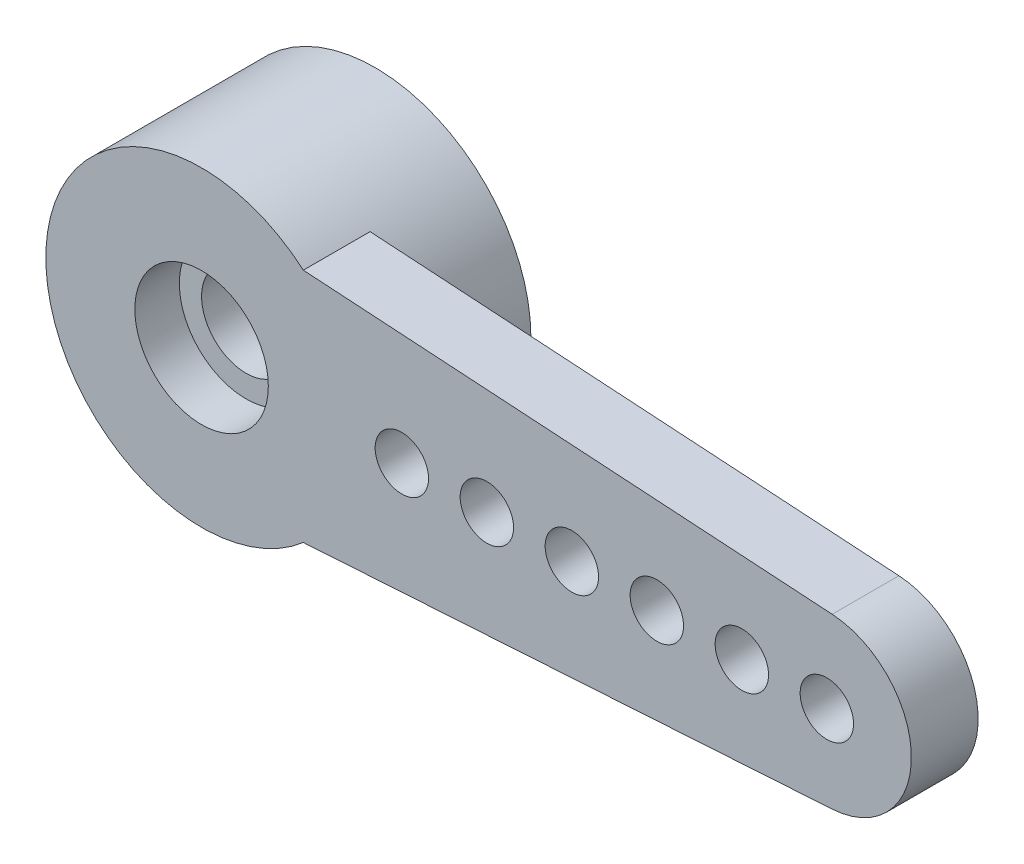
SolidWorks part; units mm, degrees
ref_plane "前视基准面" through (0, 0, 0) normal (0, 0, 1) x (1, 0, 0)
ref_plane "上视基准面" through (0, 0, 0) normal (0, 1, 0) x (1, 0, 0)
ref_plane "右视基准面" through (0, 0, 0) normal (1, 0, 0) x (0, 0, -1)
other "Configuration Table"
sketch "草图1" plane through (0, 0, 0) normal (0, 0, 1) x (1, 0, 0)
  line L12 (15.95, 15.99) -> (15.95, -15.1175) construction
  line L13 (0, 0) -> (14.05, 0) construction
  line L14 (2.2864, 2.65) -> (14.1703, 1.8962)
  line L15 (14.1703, -1.8962) -> (2.2864, -2.65)
  line L16 (2.2864, 2.65) -> (2.2864, -2.65)
  line L17 (4.5, 0) -> (6.41, 0)
  line L18 (6.41, 0) -> (8.32, 0)
  line L19 (8.32, 0) -> (10.23, 0)
  line L20 (10.23, 0) -> (12.14, 0)
  line L21 (12.14, 0) -> (14.05, 0)
  line L22 (-3.5, 5.9995) -> (-3.5, -4.0704) construction
  line L23 (4.5, 6.4068) -> (4.5, 4.4679) construction
  circle A0 centre (0, 0) radius 3.5
  circle A1 centre (0, 0) radius 1.5
  circle A2 centre (0, 0) radius 1
  circle A3 centre (0, 0) radius 2.5
  circle A4 centre (14.05, 0) radius 1.9
  circle A5 centre (14.05, 0) radius 0.6
  circle A6 centre (4.5, 0) radius 0.6
  circle A7 centre (6.41, 0) radius 0.6
  circle A8 centre (8.32, 0) radius 0.6
  circle A9 centre (10.23, 0) radius 0.6
  circle A10 centre (12.14, 0) radius 0.6
  dimension "D1" = 7
  dimension "D2" = 5
  dimension "D3" = 2
  dimension "D4" = 3
  dimension "D6" = 3.8
  dimension "D8" = 1.2
  dimension "D5" = 15.95
  dimension "D7" = 5.3
  dimension "D9" = 8
extrude "凸台-拉伸1" add sketch "草图1" along normal blind 3.9 contours A0
extrude "凸台-拉伸2" add sketch "草图1<6>" against normal blind 1.5 from surface contours A10 A4 L14 A0 L15 A9 A8 A7 A6 | A10 A5 A4 region at (8.2201, 2.1432, 0) region at (15.3967, 1.264, 0) starting at face at (3.5, 0, 3.9)
sketch "草图1<6>" plane through (0, 0, 0) normal (0, 0, 1) x (1, 0, 0) same geometry as "草图1"
extrude "切除-拉伸1" cut sketch "草图1<3>" along normal blind 2 contours A3
sketch "草图1<3>" plane through (0, 0, 0) normal (0, 0, 1) x (1, 0, 0) same geometry as "草图1"
extrude "切除-拉伸2" cut sketch "草图1<4>" against normal blind 1 from surface contours A1 starting at face at (7.2267, 0, 3.9)
sketch "草图1<4>" plane through (0, 0, 0) normal (0, 0, 1) x (1, 0, 0) same geometry as "草图1"
extrude "切除-拉伸3" cut sketch "草图1<5>" along normal through all contours A2
sketch "草图1<5>" plane through (0, 0, 0) normal (0, 0, 1) x (1, 0, 0) same geometry as "草图1"
